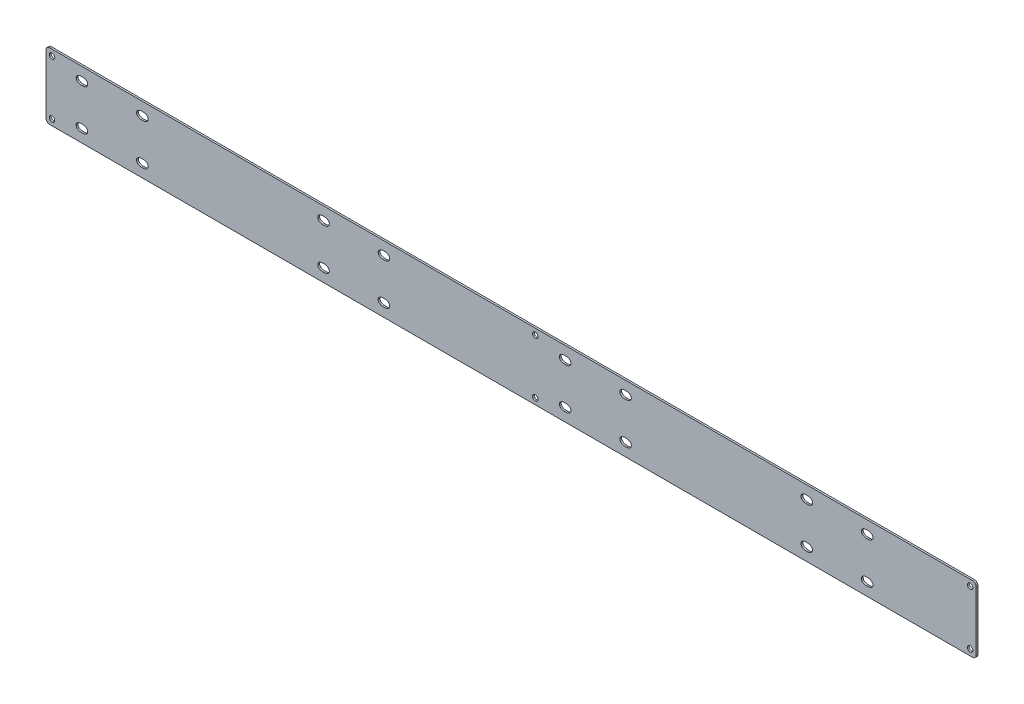
SolidWorks part; units mm, degrees
note: The reader was unsure of these and kept them because the rebuilt part matched: thickness of "Базовая кромка1", "Листовой металл3", "Листовой металл13".
material "AISI 1020 Сталь, холоднокатаная"
ref_plane "Спереди" through (0, 0, 0) normal (0, 0, 1) x (1, 0, 0)
ref_plane "Сверху" through (0, 0, 0) normal (0, 1, 0) x (1, 0, 0)
ref_plane "Справа" through (0, 0, 0) normal (1, 0, 0) x (0, 0, -1)
sketch "Эскиз1" plane through (0, 0, 0) normal (0, 0, 1) x (1, 0, 0)
  line L0 (-4321.9393, -51.3277) -> (-3551.9393, -51.3277) construction
  line L1 (-4321.9393, -23.8277) -> (-3551.9393, -23.8277)
  line L2 (-4321.9393, -23.8277) -> (-4321.9393, -78.8277)
  line L3 (-4321.9393, -78.8277) -> (-3551.9393, -78.8277)
  line L4 (-3551.9393, -23.8277) -> (-3551.9393, -78.8277)
  line L5 (-3936.9393, -23.8277) -> (-3936.9393, -78.8277) construction
  spline B0 degree 3 poles (-4296.9393, -68.2867) (-4296.9485, -68.1892) (-4296.9509, -68.093) (-4296.9471, -67.9985) (-4296.8907, -66.5881) (-4295.5737, -65.2085) (-4292.9393, -65.1458) knots 0.977241 0.977241 0.977241 0.977241 1 1 1 1.238728 1.238728 1.238728 1.238728 weights 0.913109 0.940691 0.969655 1 0.681696 0.515369 0.501017
  line B1 (-4292.9393, -65.1458) -> (-4291.4393, -65.1458)
  spline B2 degree 3 poles (-4287.4393, -68.2867) (-4287.43, -68.1892) (-4287.4276, -68.093) (-4287.4314, -67.9985) (-4287.4879, -66.5881) (-4288.8049, -65.2085) (-4291.4393, -65.1458) knots 0.977241 0.977241 0.977241 0.977241 1 1 1 1.238728 1.238728 1.238728 1.238728 weights 0.913109 0.940691 0.969655 1 0.681696 0.515369 0.501017
  line B3 (-4296.9393, -68.2867) -> (-4287.4393, -68.2867) construction
  line B4 (-4292.9393, -71.4277) -> (-4291.4393, -71.4277)
  spline B5 degree 3 poles (-4296.9393, -68.2867) (-4296.9485, -68.3843) (-4296.9509, -68.4804) (-4296.9471, -68.575) (-4296.8907, -69.9854) (-4295.5737, -71.365) (-4292.9393, -71.4277) knots 0.977241 0.977241 0.977241 0.977241 1 1 1 1.238728 1.238728 1.238728 1.238728 weights 0.913109 0.940691 0.969655 1 0.681696 0.515369 0.501017
  spline B6 degree 3 poles (-4287.4393, -68.2867) (-4287.43, -68.3843) (-4287.4276, -68.4804) (-4287.4314, -68.575) (-4287.4879, -69.9854) (-4288.8049, -71.365) (-4291.4393, -71.4277) knots 0.977241 0.977241 0.977241 0.977241 1 1 1 1.238728 1.238728 1.238728 1.238728 weights 0.913109 0.940691 0.969655 1 0.681696 0.515369 0.501017
  spline B7 degree 3 poles (-4296.9393, -34.3686) (-4296.9485, -34.4662) (-4296.9509, -34.5623) (-4296.9471, -34.6569) (-4296.8907, -36.0673) (-4295.5737, -37.4469) (-4292.9393, -37.5096) knots 0.977241 0.977241 0.977241 0.977241 1 1 1 1.238728 1.238728 1.238728 1.238728 weights 0.913109 0.940691 0.969655 1 0.681696 0.515369 0.501017
  line B8 (-4292.9393, -37.5096) -> (-4291.4393, -37.5096)
  spline B9 degree 3 poles (-4287.4393, -34.3686) (-4287.43, -34.4662) (-4287.4276, -34.5623) (-4287.4314, -34.6569) (-4287.4879, -36.0673) (-4288.8049, -37.4469) (-4291.4393, -37.5096) knots 0.977241 0.977241 0.977241 0.977241 1 1 1 1.238728 1.238728 1.238728 1.238728 weights 0.913109 0.940691 0.969655 1 0.681696 0.515369 0.501017
  line B10 (-4292.9393, -31.2277) -> (-4291.4393, -31.2277)
  spline B11 degree 3 poles (-4296.9393, -34.3686) (-4296.9485, -34.2711) (-4296.9509, -34.1749) (-4296.9471, -34.0804) (-4296.8907, -32.67) (-4295.5737, -31.2904) (-4292.9393, -31.2277) knots 0.977241 0.977241 0.977241 0.977241 1 1 1 1.238728 1.238728 1.238728 1.238728 weights 0.913109 0.940691 0.969655 1 0.681696 0.515369 0.501017
  spline B12 degree 3 poles (-4287.4393, -34.3686) (-4287.43, -34.2711) (-4287.4276, -34.1749) (-4287.4314, -34.0804) (-4287.4879, -32.67) (-4288.8049, -31.2904) (-4291.4393, -31.2277) knots 0.977241 0.977241 0.977241 0.977241 1 1 1 1.238728 1.238728 1.238728 1.238728 weights 0.913109 0.940691 0.969655 1 0.681696 0.515369 0.501017
  spline B13 degree 3 poles (-4246.9393, -68.2867) (-4246.9485, -68.1892) (-4246.9509, -68.093) (-4246.9471, -67.9985) (-4246.8907, -66.5881) (-4245.5737, -65.2085) (-4242.9393, -65.1458) knots 0.977241 0.977241 0.977241 0.977241 1 1 1 1.238728 1.238728 1.238728 1.238728 weights 0.913109 0.940691 0.969655 1 0.681696 0.515369 0.501017
  line B14 (-4242.9393, -65.1458) -> (-4241.4393, -65.1458)
  spline B15 degree 3 poles (-4237.4393, -68.2867) (-4237.43, -68.1892) (-4237.4276, -68.093) (-4237.4314, -67.9985) (-4237.4879, -66.5881) (-4238.8049, -65.2085) (-4241.4393, -65.1458) knots 0.977241 0.977241 0.977241 0.977241 1 1 1 1.238728 1.238728 1.238728 1.238728 weights 0.913109 0.940691 0.969655 1 0.681696 0.515369 0.501017
  line B16 (-4242.9393, -71.4277) -> (-4241.4393, -71.4277)
  spline B17 degree 3 poles (-4246.9393, -68.2867) (-4246.9485, -68.3843) (-4246.9509, -68.4804) (-4246.9471, -68.575) (-4246.8907, -69.9854) (-4245.5737, -71.365) (-4242.9393, -71.4277) knots 0.977241 0.977241 0.977241 0.977241 1 1 1 1.238728 1.238728 1.238728 1.238728 weights 0.913109 0.940691 0.969655 1 0.681696 0.515369 0.501017
  spline B18 degree 3 poles (-4237.4393, -68.2867) (-4237.43, -68.3843) (-4237.4276, -68.4804) (-4237.4314, -68.575) (-4237.4879, -69.9854) (-4238.8049, -71.365) (-4241.4393, -71.4277) knots 0.977241 0.977241 0.977241 0.977241 1 1 1 1.238728 1.238728 1.238728 1.238728 weights 0.913109 0.940691 0.969655 1 0.681696 0.515369 0.501017
  spline B19 degree 3 poles (-4246.9393, -34.3686) (-4246.9485, -34.4662) (-4246.9509, -34.5623) (-4246.9471, -34.6569) (-4246.8907, -36.0673) (-4245.5737, -37.4469) (-4242.9393, -37.5096) knots 0.977241 0.977241 0.977241 0.977241 1 1 1 1.238728 1.238728 1.238728 1.238728 weights 0.913109 0.940691 0.969655 1 0.681696 0.515369 0.501017
  line B20 (-4242.9393, -37.5096) -> (-4241.4393, -37.5096)
  spline B21 degree 3 poles (-4237.4393, -34.3686) (-4237.43, -34.4662) (-4237.4276, -34.5623) (-4237.4314, -34.6569) (-4237.4879, -36.0673) (-4238.8049, -37.4469) (-4241.4393, -37.5096) knots 0.977241 0.977241 0.977241 0.977241 1 1 1 1.238728 1.238728 1.238728 1.238728 weights 0.913109 0.940691 0.969655 1 0.681696 0.515369 0.501017
  line B22 (-4242.9393, -31.2277) -> (-4241.4393, -31.2277)
  spline B23 degree 3 poles (-4246.9393, -34.3686) (-4246.9485, -34.2711) (-4246.9509, -34.1749) (-4246.9471, -34.0804) (-4246.8907, -32.67) (-4245.5737, -31.2904) (-4242.9393, -31.2277) knots 0.977241 0.977241 0.977241 0.977241 1 1 1 1.238728 1.238728 1.238728 1.238728 weights 0.913109 0.940691 0.969655 1 0.681696 0.515369 0.501017
  spline B24 degree 3 poles (-4237.4393, -34.3686) (-4237.43, -34.2711) (-4237.4276, -34.1749) (-4237.4314, -34.0804) (-4237.4879, -32.67) (-4238.8049, -31.2904) (-4241.4393, -31.2277) knots 0.977241 0.977241 0.977241 0.977241 1 1 1 1.238728 1.238728 1.238728 1.238728 weights 0.913109 0.940691 0.969655 1 0.681696 0.515369 0.501017
  spline B25 degree 3 poles (-4096.9393, -68.2867) (-4096.9485, -68.1892) (-4096.9509, -68.093) (-4096.9471, -67.9985) (-4096.8907, -66.5881) (-4095.5737, -65.2085) (-4092.9393, -65.1458) knots 0.977241 0.977241 0.977241 0.977241 1 1 1 1.238728 1.238728 1.238728 1.238728 weights 0.913109 0.940691 0.969655 1 0.681696 0.515369 0.501017
  line B26 (-4092.9393, -65.1458) -> (-4091.4393, -65.1458)
  spline B27 degree 3 poles (-4087.4393, -68.2867) (-4087.43, -68.1892) (-4087.4276, -68.093) (-4087.4314, -67.9985) (-4087.4879, -66.5881) (-4088.8049, -65.2085) (-4091.4393, -65.1458) knots 0.977241 0.977241 0.977241 0.977241 1 1 1 1.238728 1.238728 1.238728 1.238728 weights 0.913109 0.940691 0.969655 1 0.681696 0.515369 0.501017
  line B28 (-4092.9393, -71.4277) -> (-4091.4393, -71.4277)
  spline B29 degree 3 poles (-4096.9393, -68.2867) (-4096.9485, -68.3843) (-4096.9509, -68.4804) (-4096.9471, -68.575) (-4096.8907, -69.9854) (-4095.5737, -71.365) (-4092.9393, -71.4277) knots 0.977241 0.977241 0.977241 0.977241 1 1 1 1.238728 1.238728 1.238728 1.238728 weights 0.913109 0.940691 0.969655 1 0.681696 0.515369 0.501017
  spline B30 degree 3 poles (-4087.4393, -68.2867) (-4087.43, -68.3843) (-4087.4276, -68.4804) (-4087.4314, -68.575) (-4087.4879, -69.9854) (-4088.8049, -71.365) (-4091.4393, -71.4277) knots 0.977241 0.977241 0.977241 0.977241 1 1 1 1.238728 1.238728 1.238728 1.238728 weights 0.913109 0.940691 0.969655 1 0.681696 0.515369 0.501017
  spline B31 degree 3 poles (-4096.9393, -34.3686) (-4096.9485, -34.4662) (-4096.9509, -34.5623) (-4096.9471, -34.6569) (-4096.8907, -36.0673) (-4095.5737, -37.4469) (-4092.9393, -37.5096) knots 0.977241 0.977241 0.977241 0.977241 1 1 1 1.238728 1.238728 1.238728 1.238728 weights 0.913109 0.940691 0.969655 1 0.681696 0.515369 0.501017
  line B32 (-4092.9393, -37.5096) -> (-4091.4393, -37.5096)
  spline B33 degree 3 poles (-4087.4393, -34.3686) (-4087.43, -34.4662) (-4087.4276, -34.5623) (-4087.4314, -34.6569) (-4087.4879, -36.0673) (-4088.8049, -37.4469) (-4091.4393, -37.5096) knots 0.977241 0.977241 0.977241 0.977241 1 1 1 1.238728 1.238728 1.238728 1.238728 weights 0.913109 0.940691 0.969655 1 0.681696 0.515369 0.501017
  line B34 (-4092.9393, -31.2277) -> (-4091.4393, -31.2277)
  spline B35 degree 3 poles (-4096.9393, -34.3686) (-4096.9485, -34.2711) (-4096.9509, -34.1749) (-4096.9471, -34.0804) (-4096.8907, -32.67) (-4095.5737, -31.2904) (-4092.9393, -31.2277) knots 0.977241 0.977241 0.977241 0.977241 1 1 1 1.238728 1.238728 1.238728 1.238728 weights 0.913109 0.940691 0.969655 1 0.681696 0.515369 0.501017
  spline B36 degree 3 poles (-4087.4393, -34.3686) (-4087.43, -34.2711) (-4087.4276, -34.1749) (-4087.4314, -34.0804) (-4087.4879, -32.67) (-4088.8049, -31.2904) (-4091.4393, -31.2277) knots 0.977241 0.977241 0.977241 0.977241 1 1 1 1.238728 1.238728 1.238728 1.238728 weights 0.913109 0.940691 0.969655 1 0.681696 0.515369 0.501017
  spline B37 degree 3 poles (-4046.9393, -68.2867) (-4046.9485, -68.1892) (-4046.9509, -68.093) (-4046.9471, -67.9985) (-4046.8907, -66.5881) (-4045.5737, -65.2085) (-4042.9393, -65.1458) knots 0.977241 0.977241 0.977241 0.977241 1 1 1 1.238728 1.238728 1.238728 1.238728 weights 0.913109 0.940691 0.969655 1 0.681696 0.515369 0.501017
  line B38 (-4042.9393, -65.1458) -> (-4041.4393, -65.1458)
  spline B39 degree 3 poles (-4037.4393, -68.2867) (-4037.43, -68.1892) (-4037.4276, -68.093) (-4037.4314, -67.9985) (-4037.4879, -66.5881) (-4038.8049, -65.2085) (-4041.4393, -65.1458) knots 0.977241 0.977241 0.977241 0.977241 1 1 1 1.238728 1.238728 1.238728 1.238728 weights 0.913109 0.940691 0.969655 1 0.681696 0.515369 0.501017
  line B40 (-4042.9393, -71.4277) -> (-4041.4393, -71.4277)
  spline B41 degree 3 poles (-4046.9393, -68.2867) (-4046.9485, -68.3843) (-4046.9509, -68.4804) (-4046.9471, -68.575) (-4046.8907, -69.9854) (-4045.5737, -71.365) (-4042.9393, -71.4277) knots 0.977241 0.977241 0.977241 0.977241 1 1 1 1.238728 1.238728 1.238728 1.238728 weights 0.913109 0.940691 0.969655 1 0.681696 0.515369 0.501017
  spline B42 degree 3 poles (-4037.4393, -68.2867) (-4037.43, -68.3843) (-4037.4276, -68.4804) (-4037.4314, -68.575) (-4037.4879, -69.9854) (-4038.8049, -71.365) (-4041.4393, -71.4277) knots 0.977241 0.977241 0.977241 0.977241 1 1 1 1.238728 1.238728 1.238728 1.238728 weights 0.913109 0.940691 0.969655 1 0.681696 0.515369 0.501017
  spline B43 degree 3 poles (-4046.9393, -34.3686) (-4046.9485, -34.4662) (-4046.9509, -34.5623) (-4046.9471, -34.6569) (-4046.8907, -36.0673) (-4045.5737, -37.4469) (-4042.9393, -37.5096) knots 0.977241 0.977241 0.977241 0.977241 1 1 1 1.238728 1.238728 1.238728 1.238728 weights 0.913109 0.940691 0.969655 1 0.681696 0.515369 0.501017
  line B44 (-4042.9393, -37.5096) -> (-4041.4393, -37.5096)
  spline B45 degree 3 poles (-4037.4393, -34.3686) (-4037.43, -34.4662) (-4037.4276, -34.5623) (-4037.4314, -34.6569) (-4037.4879, -36.0673) (-4038.8049, -37.4469) (-4041.4393, -37.5096) knots 0.977241 0.977241 0.977241 0.977241 1 1 1 1.238728 1.238728 1.238728 1.238728 weights 0.913109 0.940691 0.969655 1 0.681696 0.515369 0.501017
  line B46 (-4042.9393, -31.2277) -> (-4041.4393, -31.2277)
  spline B47 degree 3 poles (-4046.9393, -34.3686) (-4046.9485, -34.2711) (-4046.9509, -34.1749) (-4046.9471, -34.0804) (-4046.8907, -32.67) (-4045.5737, -31.2904) (-4042.9393, -31.2277) knots 0.977241 0.977241 0.977241 0.977241 1 1 1 1.238728 1.238728 1.238728 1.238728 weights 0.913109 0.940691 0.969655 1 0.681696 0.515369 0.501017
  spline B48 degree 3 poles (-4037.4393, -34.3686) (-4037.43, -34.2711) (-4037.4276, -34.1749) (-4037.4314, -34.0804) (-4037.4879, -32.67) (-4038.8049, -31.2904) (-4041.4393, -31.2277) knots 0.977241 0.977241 0.977241 0.977241 1 1 1 1.238728 1.238728 1.238728 1.238728 weights 0.913109 0.940691 0.969655 1 0.681696 0.515369 0.501017
  spline B49 degree 3 poles (-3896.9393, -68.2867) (-3896.9485, -68.1892) (-3896.9509, -68.093) (-3896.9471, -67.9985) (-3896.8907, -66.5881) (-3895.5737, -65.2085) (-3892.9393, -65.1458) knots 0.977241 0.977241 0.977241 0.977241 1 1 1 1.238728 1.238728 1.238728 1.238728 weights 0.913109 0.940691 0.969655 1 0.681696 0.515369 0.501017
  line B50 (-3892.9393, -65.1458) -> (-3891.4393, -65.1458)
  spline B51 degree 3 poles (-3887.4393, -68.2867) (-3887.43, -68.1892) (-3887.4276, -68.093) (-3887.4314, -67.9985) (-3887.4879, -66.5881) (-3888.8049, -65.2085) (-3891.4393, -65.1458) knots 0.977241 0.977241 0.977241 0.977241 1 1 1 1.238728 1.238728 1.238728 1.238728 weights 0.913109 0.940691 0.969655 1 0.681696 0.515369 0.501017
  line B52 (-3892.9393, -71.4277) -> (-3891.4393, -71.4277)
  spline B53 degree 3 poles (-3896.9393, -68.2867) (-3896.9485, -68.3843) (-3896.9509, -68.4804) (-3896.9471, -68.575) (-3896.8907, -69.9854) (-3895.5737, -71.365) (-3892.9393, -71.4277) knots 0.977241 0.977241 0.977241 0.977241 1 1 1 1.238728 1.238728 1.238728 1.238728 weights 0.913109 0.940691 0.969655 1 0.681696 0.515369 0.501017
  spline B54 degree 3 poles (-3887.4393, -68.2867) (-3887.43, -68.3843) (-3887.4276, -68.4804) (-3887.4314, -68.575) (-3887.4879, -69.9854) (-3888.8049, -71.365) (-3891.4393, -71.4277) knots 0.977241 0.977241 0.977241 0.977241 1 1 1 1.238728 1.238728 1.238728 1.238728 weights 0.913109 0.940691 0.969655 1 0.681696 0.515369 0.501017
  spline B55 degree 3 poles (-3896.9393, -34.3686) (-3896.9485, -34.4662) (-3896.9509, -34.5623) (-3896.9471, -34.6569) (-3896.8907, -36.0673) (-3895.5737, -37.4469) (-3892.9393, -37.5096) knots 0.977241 0.977241 0.977241 0.977241 1 1 1 1.238728 1.238728 1.238728 1.238728 weights 0.913109 0.940691 0.969655 1 0.681696 0.515369 0.501017
  line B56 (-3892.9393, -37.5096) -> (-3891.4393, -37.5096)
  spline B57 degree 3 poles (-3887.4393, -34.3686) (-3887.43, -34.4662) (-3887.4276, -34.5623) (-3887.4314, -34.6569) (-3887.4879, -36.0673) (-3888.8049, -37.4469) (-3891.4393, -37.5096) knots 0.977241 0.977241 0.977241 0.977241 1 1 1 1.238728 1.238728 1.238728 1.238728 weights 0.913109 0.940691 0.969655 1 0.681696 0.515369 0.501017
  line B58 (-3892.9393, -31.2277) -> (-3891.4393, -31.2277)
  spline B59 degree 3 poles (-3896.9393, -34.3686) (-3896.9485, -34.2711) (-3896.9509, -34.1749) (-3896.9471, -34.0804) (-3896.8907, -32.67) (-3895.5737, -31.2904) (-3892.9393, -31.2277) knots 0.977241 0.977241 0.977241 0.977241 1 1 1 1.238728 1.238728 1.238728 1.238728 weights 0.913109 0.940691 0.969655 1 0.681696 0.515369 0.501017
  spline B60 degree 3 poles (-3887.4393, -34.3686) (-3887.43, -34.2711) (-3887.4276, -34.1749) (-3887.4314, -34.0804) (-3887.4879, -32.67) (-3888.8049, -31.2904) (-3891.4393, -31.2277) knots 0.977241 0.977241 0.977241 0.977241 1 1 1 1.238728 1.238728 1.238728 1.238728 weights 0.913109 0.940691 0.969655 1 0.681696 0.515369 0.501017
  spline B61 degree 3 poles (-3846.9393, -68.2867) (-3846.9485, -68.1892) (-3846.9509, -68.093) (-3846.9471, -67.9985) (-3846.8907, -66.5881) (-3845.5737, -65.2085) (-3842.9393, -65.1458) knots 0.977241 0.977241 0.977241 0.977241 1 1 1 1.238728 1.238728 1.238728 1.238728 weights 0.913109 0.940691 0.969655 1 0.681696 0.515369 0.501017
  line B62 (-3842.9393, -65.1458) -> (-3841.4393, -65.1458)
  spline B63 degree 3 poles (-3837.4393, -68.2867) (-3837.43, -68.1892) (-3837.4276, -68.093) (-3837.4314, -67.9985) (-3837.4879, -66.5881) (-3838.8049, -65.2085) (-3841.4393, -65.1458) knots 0.977241 0.977241 0.977241 0.977241 1 1 1 1.238728 1.238728 1.238728 1.238728 weights 0.913109 0.940691 0.969655 1 0.681696 0.515369 0.501017
  line B64 (-3842.9393, -71.4277) -> (-3841.4393, -71.4277)
  spline B65 degree 3 poles (-3846.9393, -68.2867) (-3846.9485, -68.3843) (-3846.9509, -68.4804) (-3846.9471, -68.575) (-3846.8907, -69.9854) (-3845.5737, -71.365) (-3842.9393, -71.4277) knots 0.977241 0.977241 0.977241 0.977241 1 1 1 1.238728 1.238728 1.238728 1.238728 weights 0.913109 0.940691 0.969655 1 0.681696 0.515369 0.501017
  spline B66 degree 3 poles (-3837.4393, -68.2867) (-3837.43, -68.3843) (-3837.4276, -68.4804) (-3837.4314, -68.575) (-3837.4879, -69.9854) (-3838.8049, -71.365) (-3841.4393, -71.4277) knots 0.977241 0.977241 0.977241 0.977241 1 1 1 1.238728 1.238728 1.238728 1.238728 weights 0.913109 0.940691 0.969655 1 0.681696 0.515369 0.501017
  spline B67 degree 3 poles (-3846.9393, -34.3686) (-3846.9485, -34.4662) (-3846.9509, -34.5623) (-3846.9471, -34.6569) (-3846.8907, -36.0673) (-3845.5737, -37.4469) (-3842.9393, -37.5096) knots 0.977241 0.977241 0.977241 0.977241 1 1 1 1.238728 1.238728 1.238728 1.238728 weights 0.913109 0.940691 0.969655 1 0.681696 0.515369 0.501017
  line B68 (-3842.9393, -37.5096) -> (-3841.4393, -37.5096)
  spline B69 degree 3 poles (-3837.4393, -34.3686) (-3837.43, -34.4662) (-3837.4276, -34.5623) (-3837.4314, -34.6569) (-3837.4879, -36.0673) (-3838.8049, -37.4469) (-3841.4393, -37.5096) knots 0.977241 0.977241 0.977241 0.977241 1 1 1 1.238728 1.238728 1.238728 1.238728 weights 0.913109 0.940691 0.969655 1 0.681696 0.515369 0.501017
  line B70 (-3842.9393, -31.2277) -> (-3841.4393, -31.2277)
  spline B71 degree 3 poles (-3846.9393, -34.3686) (-3846.9485, -34.2711) (-3846.9509, -34.1749) (-3846.9471, -34.0804) (-3846.8907, -32.67) (-3845.5737, -31.2904) (-3842.9393, -31.2277) knots 0.977241 0.977241 0.977241 0.977241 1 1 1 1.238728 1.238728 1.238728 1.238728 weights 0.913109 0.940691 0.969655 1 0.681696 0.515369 0.501017
  spline B72 degree 3 poles (-3837.4393, -34.3686) (-3837.43, -34.2711) (-3837.4276, -34.1749) (-3837.4314, -34.0804) (-3837.4879, -32.67) (-3838.8049, -31.2904) (-3841.4393, -31.2277) knots 0.977241 0.977241 0.977241 0.977241 1 1 1 1.238728 1.238728 1.238728 1.238728 weights 0.913109 0.940691 0.969655 1 0.681696 0.515369 0.501017
  spline B73 degree 3 poles (-3696.9393, -68.2867) (-3696.9485, -68.1892) (-3696.9509, -68.093) (-3696.9471, -67.9985) (-3696.8907, -66.5881) (-3695.5737, -65.2085) (-3692.9393, -65.1458) knots 0.977241 0.977241 0.977241 0.977241 1 1 1 1.238728 1.238728 1.238728 1.238728 weights 0.913109 0.940691 0.969655 1 0.681696 0.515369 0.501017
  line B74 (-3692.9393, -65.1458) -> (-3691.4393, -65.1458)
  spline B75 degree 3 poles (-3687.4393, -68.2867) (-3687.43, -68.1892) (-3687.4276, -68.093) (-3687.4314, -67.9985) (-3687.4879, -66.5881) (-3688.8049, -65.2085) (-3691.4393, -65.1458) knots 0.977241 0.977241 0.977241 0.977241 1 1 1 1.238728 1.238728 1.238728 1.238728 weights 0.913109 0.940691 0.969655 1 0.681696 0.515369 0.501017
  line B76 (-3692.9393, -71.4277) -> (-3691.4393, -71.4277)
  spline B77 degree 3 poles (-3696.9393, -68.2867) (-3696.9485, -68.3843) (-3696.9509, -68.4804) (-3696.9471, -68.575) (-3696.8907, -69.9854) (-3695.5737, -71.365) (-3692.9393, -71.4277) knots 0.977241 0.977241 0.977241 0.977241 1 1 1 1.238728 1.238728 1.238728 1.238728 weights 0.913109 0.940691 0.969655 1 0.681696 0.515369 0.501017
  spline B78 degree 3 poles (-3687.4393, -68.2867) (-3687.43, -68.3843) (-3687.4276, -68.4804) (-3687.4314, -68.575) (-3687.4879, -69.9854) (-3688.8049, -71.365) (-3691.4393, -71.4277) knots 0.977241 0.977241 0.977241 0.977241 1 1 1 1.238728 1.238728 1.238728 1.238728 weights 0.913109 0.940691 0.969655 1 0.681696 0.515369 0.501017
  spline B79 degree 3 poles (-3696.9393, -34.3686) (-3696.9485, -34.4662) (-3696.9509, -34.5623) (-3696.9471, -34.6569) (-3696.8907, -36.0673) (-3695.5737, -37.4469) (-3692.9393, -37.5096) knots 0.977241 0.977241 0.977241 0.977241 1 1 1 1.238728 1.238728 1.238728 1.238728 weights 0.913109 0.940691 0.969655 1 0.681696 0.515369 0.501017
  line B80 (-3692.9393, -37.5096) -> (-3691.4393, -37.5096)
  spline B81 degree 3 poles (-3687.4393, -34.3686) (-3687.43, -34.4662) (-3687.4276, -34.5623) (-3687.4314, -34.6569) (-3687.4879, -36.0673) (-3688.8049, -37.4469) (-3691.4393, -37.5096) knots 0.977241 0.977241 0.977241 0.977241 1 1 1 1.238728 1.238728 1.238728 1.238728 weights 0.913109 0.940691 0.969655 1 0.681696 0.515369 0.501017
  line B82 (-3692.9393, -31.2277) -> (-3691.4393, -31.2277)
  spline B83 degree 3 poles (-3696.9393, -34.3686) (-3696.9485, -34.2711) (-3696.9509, -34.1749) (-3696.9471, -34.0804) (-3696.8907, -32.67) (-3695.5737, -31.2904) (-3692.9393, -31.2277) knots 0.977241 0.977241 0.977241 0.977241 1 1 1 1.238728 1.238728 1.238728 1.238728 weights 0.913109 0.940691 0.969655 1 0.681696 0.515369 0.501017
  spline B84 degree 3 poles (-3687.4393, -34.3686) (-3687.43, -34.2711) (-3687.4276, -34.1749) (-3687.4314, -34.0804) (-3687.4879, -32.67) (-3688.8049, -31.2904) (-3691.4393, -31.2277) knots 0.977241 0.977241 0.977241 0.977241 1 1 1 1.238728 1.238728 1.238728 1.238728 weights 0.913109 0.940691 0.969655 1 0.681696 0.515369 0.501017
  spline B85 degree 3 poles (-3646.9393, -68.2867) (-3646.9485, -68.1892) (-3646.9509, -68.093) (-3646.9471, -67.9985) (-3646.8907, -66.5881) (-3645.5737, -65.2085) (-3642.9393, -65.1458) knots 0.977241 0.977241 0.977241 0.977241 1 1 1 1.238728 1.238728 1.238728 1.238728 weights 0.913109 0.940691 0.969655 1 0.681696 0.515369 0.501017
  line B86 (-3642.9393, -65.1458) -> (-3641.4393, -65.1458)
  spline B87 degree 3 poles (-3637.4393, -68.2867) (-3637.43, -68.1892) (-3637.4276, -68.093) (-3637.4314, -67.9985) (-3637.4879, -66.5881) (-3638.8049, -65.2085) (-3641.4393, -65.1458) knots 0.977241 0.977241 0.977241 0.977241 1 1 1 1.238728 1.238728 1.238728 1.238728 weights 0.913109 0.940691 0.969655 1 0.681696 0.515369 0.501017
  line B88 (-3642.9393, -71.4277) -> (-3641.4393, -71.4277)
  spline B89 degree 3 poles (-3646.9393, -68.2867) (-3646.9485, -68.3843) (-3646.9509, -68.4804) (-3646.9471, -68.575) (-3646.8907, -69.9854) (-3645.5737, -71.365) (-3642.9393, -71.4277) knots 0.977241 0.977241 0.977241 0.977241 1 1 1 1.238728 1.238728 1.238728 1.238728 weights 0.913109 0.940691 0.969655 1 0.681696 0.515369 0.501017
  spline B90 degree 3 poles (-3637.4393, -68.2867) (-3637.43, -68.3843) (-3637.4276, -68.4804) (-3637.4314, -68.575) (-3637.4879, -69.9854) (-3638.8049, -71.365) (-3641.4393, -71.4277) knots 0.977241 0.977241 0.977241 0.977241 1 1 1 1.238728 1.238728 1.238728 1.238728 weights 0.913109 0.940691 0.969655 1 0.681696 0.515369 0.501017
  spline B91 degree 3 poles (-3646.9393, -34.3686) (-3646.9485, -34.4662) (-3646.9509, -34.5623) (-3646.9471, -34.6569) (-3646.8907, -36.0673) (-3645.5737, -37.4469) (-3642.9393, -37.5096) knots 0.977241 0.977241 0.977241 0.977241 1 1 1 1.238728 1.238728 1.238728 1.238728 weights 0.913109 0.940691 0.969655 1 0.681696 0.515369 0.501017
  line B92 (-3642.9393, -37.5096) -> (-3641.4393, -37.5096)
  spline B93 degree 3 poles (-3637.4393, -34.3686) (-3637.43, -34.4662) (-3637.4276, -34.5623) (-3637.4314, -34.6569) (-3637.4879, -36.0673) (-3638.8049, -37.4469) (-3641.4393, -37.5096) knots 0.977241 0.977241 0.977241 0.977241 1 1 1 1.238728 1.238728 1.238728 1.238728 weights 0.913109 0.940691 0.969655 1 0.681696 0.515369 0.501017
  line B94 (-3642.9393, -31.2277) -> (-3641.4393, -31.2277)
  spline B95 degree 3 poles (-3646.9393, -34.3686) (-3646.9485, -34.2711) (-3646.9509, -34.1749) (-3646.9471, -34.0804) (-3646.8907, -32.67) (-3645.5737, -31.2904) (-3642.9393, -31.2277) knots 0.977241 0.977241 0.977241 0.977241 1 1 1 1.238728 1.238728 1.238728 1.238728 weights 0.913109 0.940691 0.969655 1 0.681696 0.515369 0.501017
  spline B96 degree 3 poles (-3637.4393, -34.3686) (-3637.43, -34.2711) (-3637.4276, -34.1749) (-3637.4314, -34.0804) (-3637.4879, -32.67) (-3638.8049, -31.2904) (-3641.4393, -31.2277) knots 0.977241 0.977241 0.977241 0.977241 1 1 1 1.238728 1.238728 1.238728 1.238728 weights 0.913109 0.940691 0.969655 1 0.681696 0.515369 0.501017
  dimension "D1" = 55
  dimension "D3" = 20.1
  dimension "D2" = 770
  dimension "D4" = 25
sketch_block_instance "Блок-Овал-1"
sketch_block "Блок-Овал" parameters "D1"=6.1595, "D2"=1.5024, "D3"=6.8347, "D4"=7.1175
sketch_block_instance "Блок-Овал-58"
sketch_block_instance "Блок-Овал-59"
sketch_block_instance "Блок-Овал-60"
sketch_block_instance "Блок-Овал-93"
sketch_block_instance "Блок-Овал-94"
sketch_block_instance "Блок-Овал-95"
sketch_block_instance "Блок-Овал-96"
sketch_block_instance "Блок-Овал-97"
sketch_block_instance "Блок-Овал-98"
sketch_block_instance "Блок-Овал-99"
sketch_block_instance "Блок-Овал-100"
sketch_block_instance "Блок-Овал-101"
sketch_block_instance "Блок-Овал-102"
sketch_block_instance "Блок-Овал-103"
sketch_block_instance "Блок-Овал-104" parameters "D1"=42.8153, "D2"=214.0763, "D3"=1650, "D4"=26.5458, "D5"=20
base flange "Базовая кромка1" sketch "Эскиз1" thickness 1.5 reverse thickness direction no parameters "D1"=0.8
sketch "Эскиз2" plane through (0, 0, 0) normal (0, 0, 1) x (1, 0, 0)
  line L0 (-3936.9393, -23.8277) -> (-3936.9393, -78.8277) construction
  line L1 (-3551.9393, -23.8277) -> (-4321.9393, -23.8277) construction
  line L2 (-4321.9393, -78.8277) -> (-3551.9393, -78.8277) construction
  line L3 (-4321.9393, -51.3277) -> (-3551.9393, -51.3277) construction
  line L4 (-4321.9393, -23.8277) -> (-4321.9393, -78.8277) construction
  line L5 (-3551.9393, -78.8277) -> (-3551.9393, -23.8277) construction
  circle A0 centre (-4316.9393, -28.8277) radius 2.25
  circle A1 centre (-4316.9393, -73.8277) radius 2.25
  circle A2 centre (-3556.9393, -73.8277) radius 2.25
  circle A3 centre (-3556.9393, -28.8277) radius 2.25
  circle A6 centre (-3916.9393, -28.8277) radius 2.25
  circle A7 centre (-3916.9393, -73.8277) radius 2.25
  dimension "D1" = 4.5
  dimension "D2" = 5
  dimension "D3" = 5
  dimension "D4" = 20
  dimension "D6" = 4.5
  dimension "D7" = 5
extrude "Вырез-Вытянуть1" cut sketch "Эскиз2" against normal blind 10 normal cut yes
sketch "Эскиз3" plane through (0, 0, 0) normal (0, 0, 1) x (1, 0, 0)
  point P0 (-4316.9393, -28.8277)
  point P1 (-4316.9393, -73.8277)
  point P3 (-3916.9393, -28.8277)
  point P5 (-3916.9393, -73.8277)
  point P7 (-3556.9393, -28.8277)
  point P9 (-3556.9393, -73.8277)
fillet "Скругление1" radius 3 4 edges at (-3551.9393, -78.8277, -0.75) (-3551.9393, -23.8277, -0.75) (-4321.9393, -78.8277, -0.75) (-4321.9393, -23.8277, -0.75)
sketch "Сгиб-Линии1" [suppressed] plane through (0, 0, 0) normal (0, 1, 0) x (1, 0, 0)
sketch "Граничная рамка1" [suppressed] plane through (0, 0, 0) normal (0, 1, 0) x (1, 0, 0)
sheet metal parameters "Листовой металл3" thickness 1.5 parameters "D1"=0.8
flat pattern "Развертка3" [suppressed]
sketch "Сгиб-Линии2" plane through (0, 0, 0) normal (0, 1, 0) x (1, 0, 0)
sketch3d "Граничная рамка2" [suppressed]
  line L0 (-178.1955, -18.9474, 0) -> (1321.8045, -18.9474, 0) construction
  line L1 (-178.1955, 41.0526, 0) -> (1321.8045, 41.0526, 0) construction
  line L2 (-178.1955, -18.9474, 0) -> (-178.1955, 41.0526, 0) construction
  line L3 (1321.8045, -18.9474, 0) -> (1321.8045, 41.0526, 0) construction
sheet metal parameters "Листовой металл13" thickness 1.5 parameters "D1"=0.8, "D7"=1
flat pattern "Развертка3"
sketch "Сгиб-Линии2" plane through (0, 0, 0) normal (0, 1, 0) x (1, 0, 0)
sketch3d "Граничная рамка2" [suppressed]
  line L0 (-4321.9393, -23.8277, 0) -> (-3551.9393, -23.8277, 0) construction
  line L1 (-4321.9393, -78.8277, 0) -> (-3551.9393, -78.8277, 0) construction
  line L2 (-4321.9393, -23.8277, 0) -> (-4321.9393, -78.8277, 0) construction
  line L3 (-3551.9393, -23.8277, 0) -> (-3551.9393, -78.8277, 0) construction
